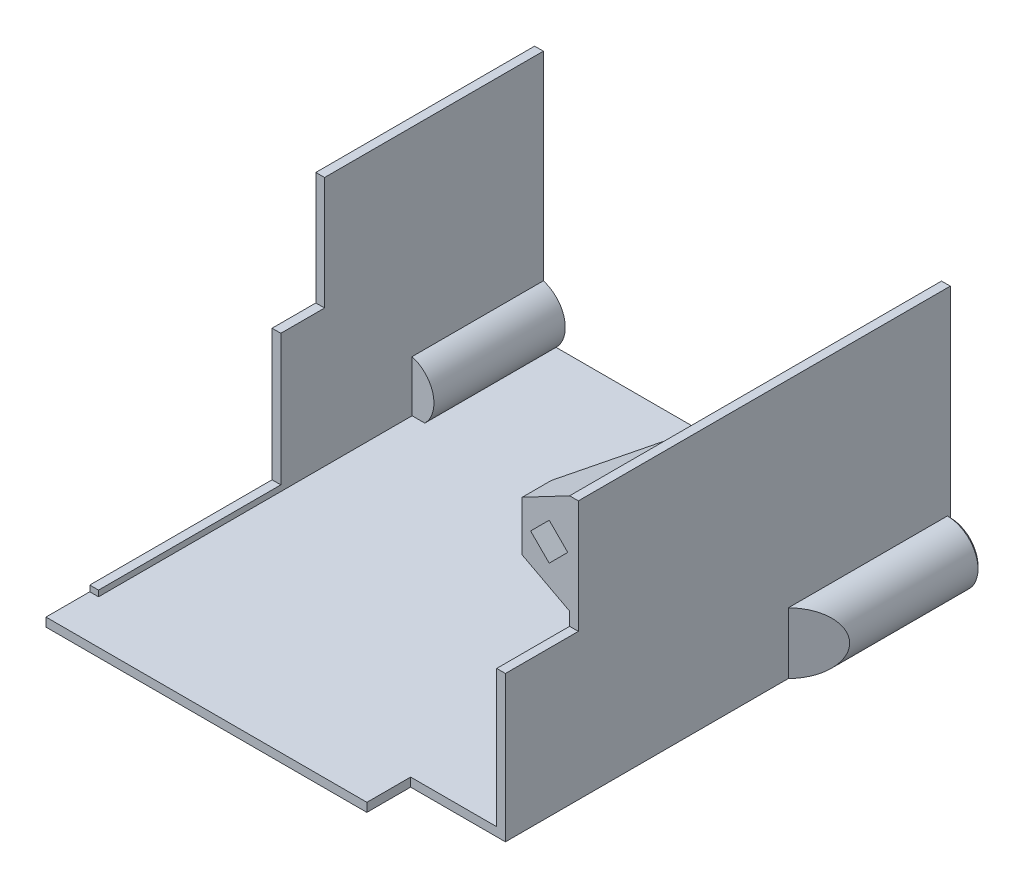
SolidWorks part; units mm, degrees
material "Custom Plastic"
ref_plane "Front Plane" through (0, 0, 0) normal (0, 0, 1) x (1, 0, 0)
ref_plane "Top Plane" through (0, 0, 0) normal (0, 1, 0) x (1, 0, 0)
ref_plane "Right Plane" through (0, 0, 0) normal (1, 0, 0) x (0, 0, -1)
sketch "Sketch1" plane through (0, 0, 0) normal (0, 0, 1) x (1, 0, 0)
  line L1 (-33.6475, 14.5475) -> (-34.8475, 14.5475)
  line L2 (-33.6475, -19.7525) -> (-33.6475, -20.9525) construction
  line L3 (-31.9081, -19.7525) -> (19.2131, -19.7525)
  line L4 (20.9525, 14.5475) -> (20.9525, -12.7276)
  line L5 (-33.6475, -12.7276) -> (-33.6475, 14.5475)
  line L7 (20.9525, 14.5475) -> (22.1525, 14.5475)
  line L8 (-34.8475, 14.5475) -> (-34.8475, -12.5525)
  line L9 (-34.8475, -20.9525) -> (22.1525, -20.9525)
  line L10 (22.1525, 14.5475) -> (22.1525, -12.5525)
  arc A0 (22.1525, -20.9525) -> (22.1525, -12.5525) centre (22.1525, -16.7525) ccw
  circle A1 centre (22.1525, -16.7525) radius 1.6 construction
  arc A2 (20.9525, -12.7276) -> (19.2131, -19.7525) centre (22.1525, -16.7525) ccw
  circle A3 centre (-34.8475, -16.7525) radius 1.6 construction
  arc A4 (-34.8475, -12.5525) -> (-34.8475, -20.9525) centre (-34.8475, -16.7525) ccw
  arc A6 (-31.9081, -19.7525) -> (-33.6475, -12.7276) centre (-34.8475, -16.7525) ccw
  dimension "D2" = 3.2
  dimension "D5" = 4.2
  dimension "D1" = 1.2
  dimension "D3" = 57
  dimension "D4" = 35.5
extrude "Boss-Extrude1" add sketch "Sketch1" along normal blind 67
sketch "Sketch2" plane through (0, 0, 67) normal (0, 0, 1) x (1, 0, 0)
  line L0 (-34.8475, -20.9525) -> (22.1525, -20.9525) construction
  line L1 (9.1525, -20.9525) -> (32.8781, -20.9525)
  line L2 (9.1525, -20.9525) -> (9.1525, -19.7525)
  line L3 (-34.8475, 12.6741) -> (32.8781, 12.6741)
  line L4 (32.8781, -20.9525) -> (32.8781, 12.6741)
  line L5 (22.1525, -12.5525) -> (22.1525, 14.5475) construction
  line L6 (9.1525, -19.7525) -> (-34.8475, -19.7525)
  line L7 (19.2131, -19.7525) -> (-31.9081, -19.7525) construction
  line L8 (-34.8475, 14.5475) -> (-34.8475, -12.5525) construction
  line L9 (-34.8475, -20.9525) -> (-34.8475, -19.7525)
  line L10 (-34.8475, -20.9525) -> (-42.7406, -20.9525)
  line L11 (-34.8475, -20.9525) -> (22.1525, -20.9525) construction
  line L12 (-42.7406, -20.9525) -> (-42.7406, -7.5075)
  line L13 (-42.7406, -7.5075) -> (-34.8475, -7.5075)
  line L14 (-34.8475, -7.5075) -> (-34.8475, 12.6741)
  dimension "D1" = 13
extrude "Cut-Extrude1" cut sketch "Sketch2" against normal blind 6
sketch "Sketch3" plane through (0, 0, 61) normal (0, 0, 1) x (1, 0, 0)
  line L0 (22.1525, -12.5525) -> (22.1525, 12.6741) construction
  line L1 (-34.8475, 14.5475) -> (22.1525, 14.5475)
  line L2 (-34.8475, 14.5475) -> (-34.8475, -0.9525)
  line L3 (-34.8475, -0.9525) -> (22.1525, -0.9525)
  line L4 (22.1525, 14.5475) -> (22.1525, -0.9525)
  dimension "D1" = 15.5
extrude "Cut-Extrude2" cut sketch "Sketch3" against normal blind 10 and the other way blind 10
sketch "Sketch4" plane through (0, 0, 51) normal (0, 0, 1) x (1, 0, 0)
  line L0 (-34.8475, 14.5475) -> (-34.8475, -0.9525) construction
  line L1 (-34.8475, 14.5475) -> (-33.6475, 14.5475)
  line L2 (-34.8475, 14.5475) -> (-34.8475, -0.9525)
  line L3 (-34.8475, -0.9525) -> (-33.6475, -0.9525)
  line L4 (-33.6475, 14.5475) -> (-33.6475, -0.9525)
extrude "Cut-Extrude3" cut sketch "Sketch4" against normal blind 21
sketch "Sketch6" plane through (0, 0, 0) normal (0, 0, -1) x (-1, 0, 0)
  circle A0 centre (-22.1525, -16.7525) radius 1.6
  circle A1 centre (34.8475, -16.7525) radius 1.6
  arc A2 (34.8475, -20.9525) -> (34.8475, -12.5525) centre (34.8475, -16.7525) ccw construction
  arc A3 (-22.1525, -12.5525) -> (-22.1525, -20.9525) centre (-22.1525, -16.7525) ccw construction
  dimension "D1" = 3.2
extrude "Cut-Extrude4" cut sketch "Sketch6" against normal blind 16
sketch "Sketch7" plane through (0, 0, 61) normal (0, 0, 1) x (1, 0, 0)
  line L0 (19.2131, -19.7525) -> (9.1525, -19.7525) construction
  line L1 (22.1525, -12.5525) -> (31.8181, -12.5525)
  line L2 (22.1525, -12.5525) -> (22.1525, -20.9525)
  line L3 (22.1525, -20.9525) -> (31.8181, -20.9525)
  line L4 (31.8181, -12.5525) -> (31.8181, -20.9525)
  line L5 (20.9525, -12.7276) -> (15.0843, -12.7276)
  line L6 (20.9525, -12.7276) -> (20.9525, -19.7525)
  line L7 (20.9525, -19.7525) -> (15.0843, -19.7525)
  line L8 (15.0843, -12.7276) -> (15.0843, -19.7525)
  line L9 (-33.6475, -12.7276) -> (-33.6475, -0.9525) construction
  line L10 (-34.8475, -20.9525) -> (-44.0251, -20.9525)
  line L11 (-34.8475, -20.9525) -> (-34.8475, -7.6032)
  line L12 (-34.8475, -7.6032) -> (-44.0251, -7.6032)
  line L13 (-44.0251, -20.9525) -> (-44.0251, -7.6032)
  line L14 (-33.6475, -7.6032) -> (-26.816, -7.6032)
  line L15 (-33.6475, -7.6032) -> (-33.6475, -19.7525)
  line L16 (-33.6475, -19.7525) -> (-26.816, -19.7525)
  line L17 (-26.816, -7.6032) -> (-26.816, -19.7525)
  line L18 (9.1525, -19.7525) -> (-34.8475, -19.7525) construction
extrude "Cut-Extrude5" cut sketch "Sketch7" against normal offset from surface (43 mm away) 18 up to face at (-36.4475, -16.7525, 0)
chamfer "Chamfer1" distance 4.2 angle 45 2 edges at (22.1525, -16.7525, 18) (-34.8475, -16.7525, 18)
chamfer "Chamfer3" distance 0.6 angle 30 2 edges at (20.5525, -16.7525, 0) (-36.4475, -16.7525, 0) first distance on face at (20.5525, -16.7525, 16) first distance on face at (-36.4475, -16.7525, 16)
chamfer "Chamfer4" distance 0.4 angle 45 3 edges at (-39.0475, -16.7525, 0) (-6.3475, -20.9525, 0) (26.3525, -16.7525, 0)
sketch "Sketch8" plane through (0, 0, 51) normal (0, 0, 1) x (1, 0, 0)
  line L0 (18.1525, 9.2975) -> (14.4525, 9.2975) construction
  line L1 (15.6025, 7.6975) -> (18.1525, 10.2475)
  line L2 (14.4525, 6.0975) -> (18.1525, 6.0975) construction
  line L4 (14.4525, 11.1225) -> (14.4525, 9.2975)
  line L5 (14.4525, 6.0975) -> (14.4525, 4.2725)
  line L7 (20.9525, 14.5475) -> (20.9525, -0.9525) construction
  line L8 (20.9525, 0.8475) -> (22.1525, 0.8475)
  line L9 (22.1525, -0.9525) -> (22.1525, 14.5475) construction
  line L10 (22.1525, 0.8475) -> (22.1525, 14.5475)
  line L11 (22.1525, 14.5475) -> (20.9525, 14.5475)
  line L12 (15.6025, 7.6975) -> (18.1525, 5.1475)
  line L13 (18.1525, 10.2475) -> (20.7025, 7.6975)
  line L14 (18.1525, 5.1475) -> (20.7025, 7.6975)
  line L15 (15.6025, 7.6975) -> (20.7025, 7.6975) construction
  line L16 (18.1525, 10.2475) -> (18.1525, 5.1475) construction
  line L17 (14.4525, 9.2975) -> (14.4525, 6.0975)
  line L18 (20.9525, 14.5475) -> (14.4525, 11.1225)
  line L19 (20.9525, 0.8475) -> (14.4525, 4.2725)
  arc A0 (18.1525, 6.0975) -> (18.1525, 9.2975) centre (18.1525, 7.6975) ccw construction
  circle A1 centre (18.1525, 7.6975) radius 2.55 construction
  dimension "D1" = 1.6
  dimension "D5" = 5.1
  dimension "D2" = 2.8
  dimension "D3" = 6.85
  dimension "D4" = 6.5
  dimension "D6" = 6.85
extrude "Boss-Extrude2" add sketch "Sketch8" against normal blind 13
sketch "Sketch10" plane through (0, 0, 38) normal (0, 0, -1) x (-1, 0, 0)
  line L0 (-18.1525, 10.6975) -> (-14.4525, 10.6975)
  line L1 (-14.4525, 11.1225) -> (-14.4525, 4.2725) construction
  line L2 (-14.4525, 10.6975) -> (-14.4525, 4.6975)
  line L3 (-14.4525, 4.6975) -> (-18.1525, 4.6975)
  line L5 (-18.1525, 10.2475) -> (-18.1525, 5.1475) construction
  arc A0 (-18.1525, 10.6975) -> (-18.1525, 4.6975) centre (-18.1525, 7.6975) ccw
  arc A1 (-18.1525, 4.6975) -> (-18.1525, 10.6975) centre (-18.1525, 7.6975) ccw construction
  dimension "D1" = 3
extrude "Cut-Extrude6" cut sketch "Sketch10" against normal offset from surface 6 and the other way blind 10 up to face at (19.4382, 6.2046, 51)
sketch "Sketch11" plane through (0, 14.5475, 0) normal (0, 1, 0) x (1, 0, 0)
  line L0 (20.9525, -38) -> (14.4525, -47)
  line L1 (14.4525, -38) -> (14.4525, -51) construction
  line L2 (14.4525, -47) -> (14.4525, -38)
  line L3 (14.4525, -38) -> (20.9525, -38)
extrude "Cut-Extrude7" cut sketch "Sketch11" against normal up to surface (10.275 mm away) up to face at (17.7025, 2.56, 44.5)
sketch "Sketch12" plane through (0, -0.9525, 0) normal (0, 1, 0) x (1, 0, 0)
  line L0 (-34.8475, -61) -> (-34.8475, -30) construction
  line L1 (-34.8475, -36) -> (-33.6475, -36)
  line L2 (-34.8475, -36) -> (-34.8475, -61)
  line L3 (-34.8475, -61) -> (-33.6475, -61)
  line L4 (-33.6475, -36) -> (-33.6475, -61)
  line L5 (-33.6475, -30) -> (-34.8475, -30) construction
  point P7 (-34.2475, -30)
  dimension "D1" = 6
extrude "Cut-Extrude8" cut sketch "Sketch12" against normal offset from surface (18 mm away) 0.8 up to face at (-8.5141, -19.7525, 37.5)
